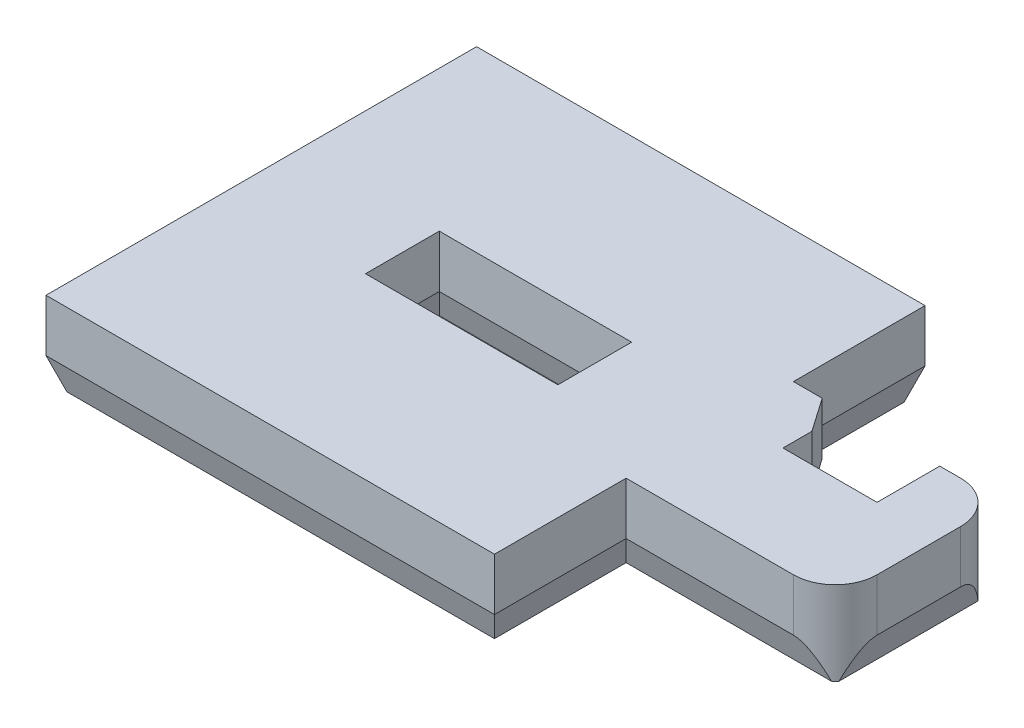
SolidWorks part; units mm, degrees
ref_plane "Front Plane" through (0, 0, 0) normal (0, 0, 1) x (1, 0, 0)
ref_plane "Top Plane" through (0, 0, 0) normal (0, 1, 0) x (1, 0, 0)
ref_plane "Right Plane" through (0, 0, 0) normal (1, 0, 0) x (0, 0, -1)
sketch "Sketch1" plane through (0, 0, 0) normal (0, 1, 0) x (1, 0, 0)
  line L1 (-11.2475, 10.2955) -> (10.2, 10.2955)
  line L2 (-11.2475, 10.2955) -> (-11.2475, -10.2955)
  line L3 (-11.2475, -10.2955) -> (10.2, -10.2955)
  line L4 (10.2, 10.2955) -> (10.2, -10.2955)
  line L6 (4.7, -1.765) -> (-4.5, -1.765)
  line L7 (4.7, -1.765) -> (4.7, 1.765)
  line L8 (4.7, 1.765) -> (-4.5, 1.765)
  line L9 (-4.5, -1.765) -> (-4.5, 1.765)
  point P11 (-4.5, 0)
  point P12 (-11.2475, 0)
  dimension "D1" = 9.2
  dimension "D2" = 3.53
  dimension "D3" = 5.5
extrude "Boss-Extrude1" add sketch "Sketch1" along normal blind 4
sketch "Sketch2" plane through (0, 0, 0) normal (0, 1, 0) x (1, 0, 0)
  line L0 (10.2, 4) -> (20.2, 4)
  line L1 (10.2, -10.2955) -> (10.2, 10.2955) construction
  line L2 (20.2, 4) -> (20.2, -4)
  line L3 (20.2, -4) -> (10.2, -4)
  line L4 (10.2, 4) -> (10.2, -4)
  point P6 (10.2, 0)
  point P7 (20.2, 0)
  dimension "D1" = 8
  dimension "D2" = 10
extrude "Boss-Extrude3" add sketch "Sketch2" along normal blind 4
sketch "Sketch3" plane through (0, 0, 0) normal (0, 1, 0) x (1, 0, 0)
  line L0 (12.7, 1) -> (12.7, 2.3845)
  line L1 (12.7, 4) -> (17.2, 4)
  line L3 (12.7, 1) -> (17.2, 1)
  line L4 (17.2, 4) -> (17.2, 1)
  line L5 (12.7, 2.3845) -> (11.5762, 4)
  line L6 (20.2, 4) -> (10.2, 4) construction
  line L7 (11.5762, 4) -> (12.7, 4)
  point P9 (12.0227, 4)
  point P10 (11.5762, 4)
  point P11 (12.8, 2.3845)
  dimension "D1" = 2.5
  dimension "D2" = 3
  dimension "D3" = 4.5
extrude "Cut-Extrude1" cut sketch "Sketch3" along normal through all
chamfer "Chamfer1" distance 1.5 distance2 0.5 17 edges at (-0.5238, 0, -10.2955) (-11.2475, 0, 0) (-0.5238, 0, 10.2955) (10.2, 0, 7.1477) (15.2, 0, 4) (20.2, 0, 0) (18.7, 0, -4) (17.2, 0, -2.5) (14.95, 0, -1) (10.2, 0, -7.1477) (0.1, 0, 1.765) (-4.5, 0, 0) (0.1, 0, -1.765) (4.7, 0, 0) (10.8881, 0, -4) (12.7, 0, -1.6923) (12.1381, 0, -3.1923) first distance on face at (-0.5238, 2, -10.2955) first distance on face at (-11.2475, 2, 0) first distance on face at (-0.5238, 2, 10.2955) first distance on face at (10.2, 2, 7.1477) first distance on face at (15.2, 2, 4) first distance on face at (20.2, 2, 0) first distance on face at (18.7, 2, -4) first distance on face at (17.2, 2, -2.5) first distance on face at (14.95, 2, -1) first distance on face at (10.2, 2, -7.1477) first distance on face at (0.1, 2, 1.765) first distance on face at (-4.5, 2, 0) first distance on face at (0.1, 2, -1.765) first distance on face at (4.7, 2, 0) first distance on face at (10.8881, 2, -4) first distance on face at (12.7, 2, -1.6923) first distance on face at (12.1381, 2, -3.1923)
fillet "Fillet1" radius 2 2 edges at (20.2, 2.75, 4) (20.2, 2.75, -4)
